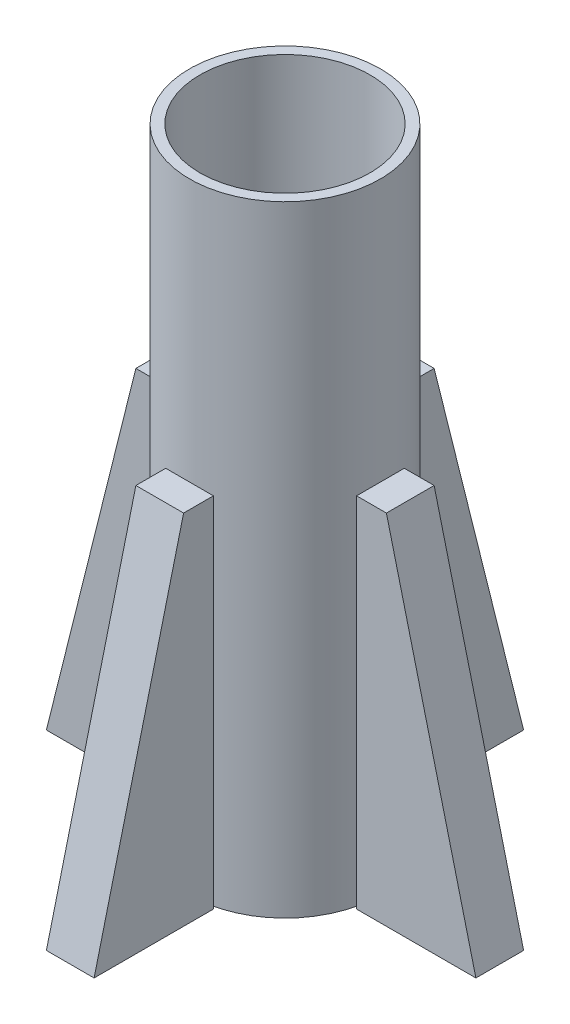
SolidWorks part; units mm, degrees
ref_plane "Front Plane" through (0, 0, 0) normal (0, 0, 1) x (1, 0, 0)
ref_plane "Top Plane" through (0, 0, 0) normal (0, 1, 0) x (1, 0, 0)
ref_plane "Right Plane" through (0, 0, 0) normal (1, 0, 0) x (0, 0, -1)
sketch "Sketch1" plane through (0, 0, 0) normal (0, 1, 0) x (1, 0, 0)
  circle A0 centre (0, 0) radius 8
  dimension "D1" = 16
extrude "Boss-Extrude1" add sketch "Sketch1" along normal blind 52
sketch "Sketch2" plane through (0, 52, 0) normal (0, 1, 0) x (1, 0, 0)
  circle A0 centre (0, 0) radius 7.125
  dimension "D1" = 14.25
extrude "Cut-Extrude1" cut sketch "Sketch2" against normal blind 50
sketch "Sketch3" plane through (0, 0, 0) normal (1, 0, 0) x (0, 0, -1)
  line L0 (-8, 30) -> (-10.5, 30)
  line L1 (-8, 52) -> (-8, 0) construction
  line L2 (-10.5, 30) -> (-18, 0)
  line L3 (-18, 0) -> (-8, 0)
  line L4 (-8, 0) -> (-8, 30)
  line L5 (8, 0) -> (18, 0)
  line L6 (18, 0) -> (10.5, 30)
  line L7 (10.5, 30) -> (8, 30)
  line L8 (8, 0) -> (8, 52) construction
  line L9 (8, 30) -> (8, 0)
  dimension "D1" = 10
  dimension "D2" = 2.5
  dimension "D3" = 10
  dimension "D4" = 2.5
  dimension "D5" = 30
  dimension "D6" = 30
extrude "Boss-Extrude2" add sketch "Sketch3" along normal blind 2 and the other way blind 2 separate body
sketch "Sketch4" plane through (0, 0, 0) normal (0, 0, 1) x (1, 0, 0)
  line L0 (8, 30) -> (10.5, 30)
  line L1 (8, 0) -> (8, 52) construction
  line L2 (10.5, 30) -> (18, 0)
  line L3 (18, 0) -> (8, 0)
  line L4 (8, 0) -> (8, 30)
  line L5 (-8, 30) -> (-8, 0)
  line L6 (-8, 52) -> (-8, 0) construction
  line L7 (-8, 0) -> (-18, 0)
  line L8 (-18, 0) -> (-10.5, 30)
  line L9 (-10.5, 30) -> (-8, 30)
  dimension "D1" = 2.5
  dimension "D2" = 10
  dimension "D3" = 30
  dimension "D4" = 10
  dimension "D5" = 2.5
  dimension "D6" = 30
extrude "Boss-Extrude3" add sketch "Sketch4" along normal blind 2 and the other way blind 2 separate body
